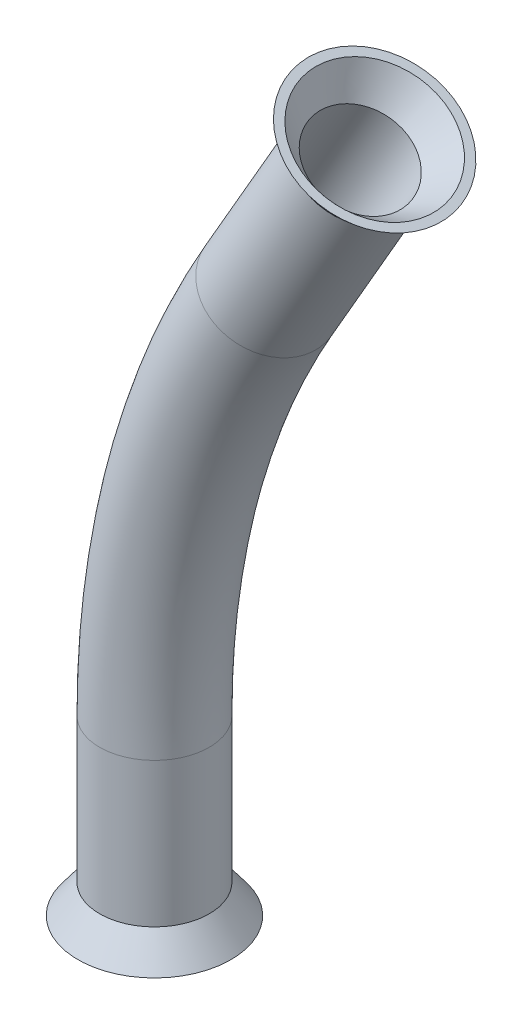
SolidWorks part; units mm, degrees
material "6061-T6 (SS)"
ref_plane "Front Plane" through (0, 0, 0) normal (0, 0, 1) x (1, 0, 0)
ref_plane "Top Plane" through (0, 0, 0) normal (0, 1, 0) x (1, 0, 0)
ref_plane "Right Plane" through (0, 0, 0) normal (1, 0, 0) x (0, 0, -1)
sketch "Sketch1" plane through (0, 0, 0) normal (0, 1, 0) x (1, 0, 0)
  circle A0 centre (0, 0) radius 4.826
  circle A1 centre (0, 0) radius 4.064
  dimension "D1" = 9.652
  dimension "D2" = 8.128
sketch "Sketch2" plane through (0, 0, 0) normal (0, 0, 1) x (1, 0, 0)
  line L0 (0, 0) -> (0, 12.7)
  line L1 (10.023, 50.1064) -> (18.1224, 64.135)
  arc A0 (0, 12.7) -> (10.023, 50.1064) centre (74.8129, 12.7) cw
  dimension "D1" = 18.1224
  dimension "D2" = 150
  dimension "D4" = 64.135
  dimension "D3" = 12.7
sweep "Sweep1" add profiles "Sketch1" path "Sketch2"
sketch "Sketch3" plane through (0, 0, 0) normal (0, -1, 0) x (1, 0, 0)
  circle A0 centre (0, 0) radius 4.826
  circle A1 centre (0, 0) radius 4.826 construction
extrude "Boss-Extrude1" add sketch "Sketch3" along normal blind 2.54 draft 37 draft outward yes
sketch "Sketch4" plane through (0, -2.54, 0) normal (0, -1, 0) x (1, 0, 0)
  line L0 (-4.826, 0) -> (-4.064, 0) construction
  line L1 (-5.978, 0) -> (-6.74, 0) construction
  circle A0 centre (0, 0) radius 5.978
  circle A1 centre (0, 0) radius 4.826 construction
  circle A2 centre (0, 0) radius 4.064 construction
  circle A3 centre (0, 0) radius 6.74 construction
extrude "Cut-Extrude1" cut sketch "Sketch4" against normal through all draft 37
sketch "Sketch5" plane through (32.3019, 55.9485, 0) normal (0.5, 0.866, 0) x (0, 0, -1)
  circle A1 centre (0, 16.373) radius 4.826
  circle A2 centre (0, 16.373) radius 4.826 construction
  circle A3 centre (0, 16.373) radius 4.826 construction
extrude "Boss-Extrude2" add sketch "Sketch5" along normal blind 2.54 draft 37 draft outward yes
sketch "Sketch6" plane through (33.5719, 58.1482, 0) normal (0.5, 0.866, 0) x (0, 0, -1)
  line L0 (-5.978, 16.373) -> (-6.74, 16.373) construction
  circle A0 centre (0, 16.373) radius 5.978
  circle A1 centre (0, 16.373) radius 6.74 construction
  dimension "D1" = 0.762
extrude "Cut-Extrude2" cut sketch "Sketch6" against normal through all draft 37
